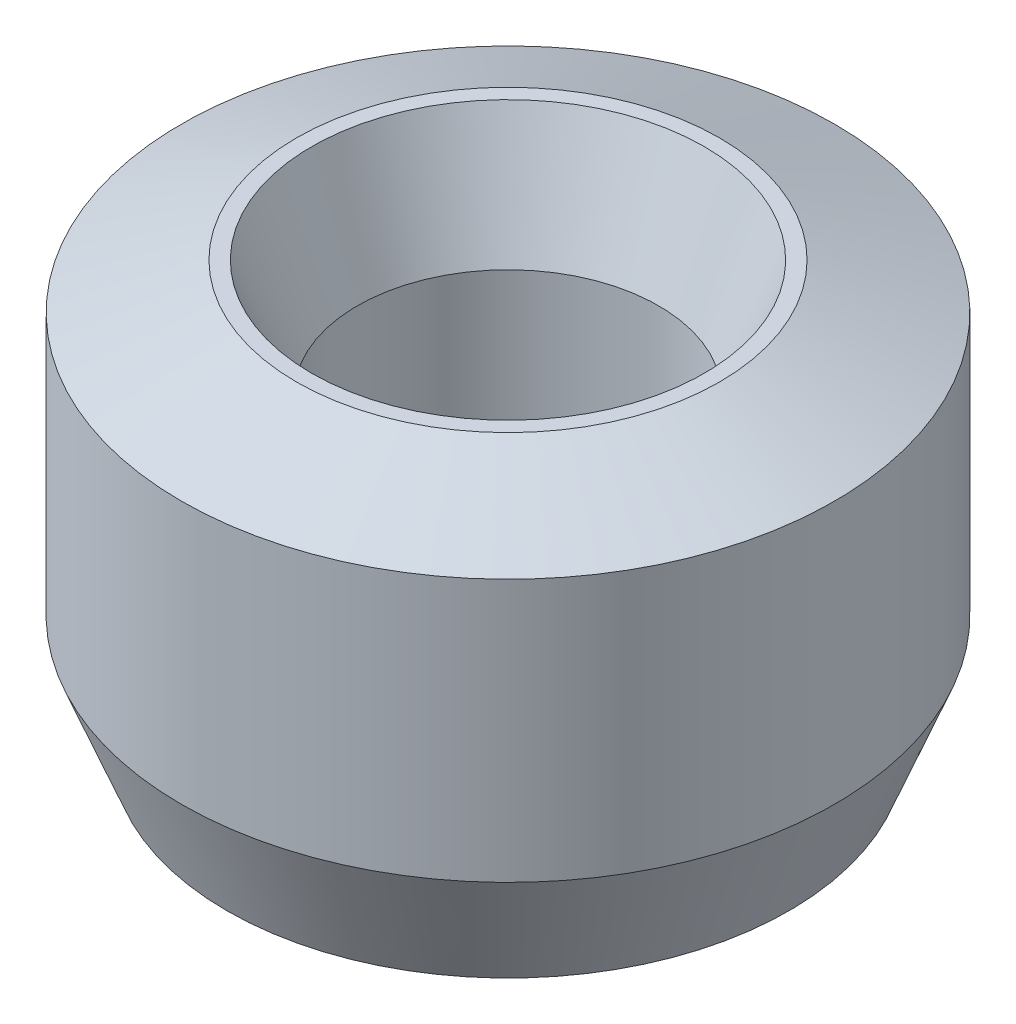
SolidWorks part; units mm, degrees
ref_plane "Front Plane" through (0, 0, 0) normal (0, 0, 1) x (1, 0, 0)
ref_plane "Top Plane" through (0, 0, 0) normal (0, 1, 0) x (1, 0, 0)
ref_plane "Right Plane" through (0, 0, 0) normal (1, 0, 0) x (0, 0, -1)
sketch "Sketch1" plane through (0, 0, 0) normal (0, 1, 0) x (1, 0, 0)
  circle A0 centre (0, 0) radius 27.5
  dimension "SLEEVE_OD" = 55
extrude "Boss-Extrude1" add sketch "Sketch1" along normal blind 35.6412
sketch "Sketch2" plane through (0, 0, 0) normal (0, 1, 0) x (1, 0, 0)
  circle A0 centre (0, 0) radius 12.6933
  dimension "BORE_D" = 25.3866
extrude "Cut-Extrude1" cut sketch "Sketch2" along normal through all
chamfer "Chamfer1" distance 3.8404 angle 68.382 4 edges at (0, 35.6412, 12.6933) (0, 0, 12.6933) (0, 0, 27.5) (0, 35.6412, 27.5) first distance on face at (0, 35.6412, 12.6933) first distance on face at (0, 0, 12.6933) first distance on face at (0, 35.6412, 27.5)
